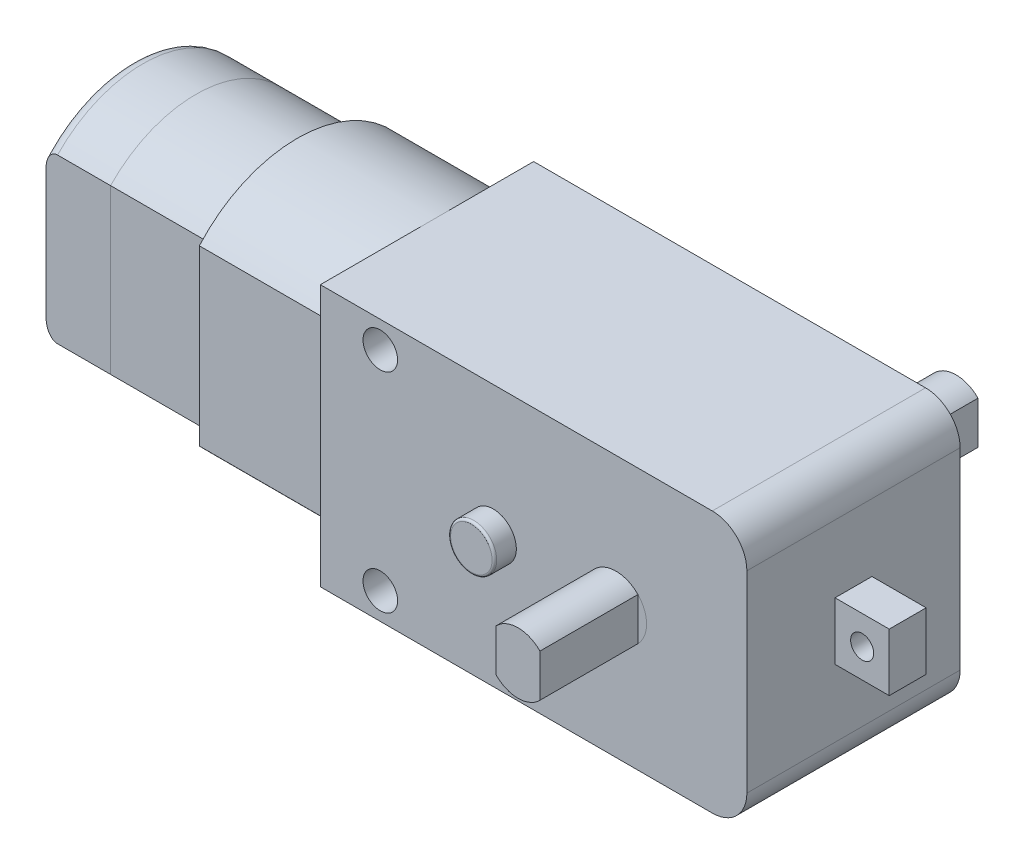
SolidWorks part; units mm, degrees
ref_plane "Alzado" through (0, 0, 0) normal (0, 0, 1) x (1, 0, 0)
ref_plane "Planta" through (0, 0, 0) normal (0, 1, 0) x (1, 0, 0)
ref_plane "Vista lateral" through (0, 0, 0) normal (1, 0, 0) x (0, 0, -1)
sketch "Croquis1" plane through (0, 0, 0) normal (0, 0, 1) x (1, 0, 0)
  line L1 (-18.5, -11.35) -> (15.5, -11.35)
  line L2 (-18.5, -11.35) -> (-18.5, 11.35)
  line L3 (-18.5, 11.35) -> (15.5, 11.35)
  line L4 (18.5, -8.35) -> (18.5, 8.35)
  line L5 (-18.5, -11.35) -> (18.5, 11.35) construction
  line L6 (-18.5, 11.35) -> (18.5, -11.35) construction
  arc A0 (15.5, -11.35) -> (18.5, -8.35) centre (15.5, -8.35) ccw
  arc A1 (15.5, 11.35) -> (18.5, 8.35) centre (15.5, 8.35) cw
  point P0 (0, 0)
  dimension "D3" = 3
  dimension "D1" = 22.7
  dimension "D2" = 37
extrude "Saliente-Extruir1" add sketch "Croquis1" along normal blind 9.25 and the other way blind 9.25
sketch "Croquis2" plane through (-18.5, 0, 0) normal (-1, 0, 0) x (0, 0, 1)
  line L0 (-0.75, -11.35) -> (-0.75, 11.35) construction
  line L1 (7.75, -7.5215) -> (7.75, 7.5215)
  line L2 (-9.25, -7.5215) -> (-9.25, 7.5215)
  line L3 (9.25, 11.35) -> (9.25, -11.35) construction
  line L5 (7.75, -12.1318) -> (7.75, 11.35) construction
  line L6 (-9.25, -12.1318) -> (-9.25, 11.35) construction
  line L7 (-0.75, -12.1318) -> (-0.75, 11.35) construction
  arc A0 (7.75, 7.5215) -> (-9.25, 7.5215) centre (-0.75, 0) ccw
  arc A1 (-9.25, -7.5215) -> (7.75, -7.5215) centre (-0.75, 0) ccw
  point P8 (-0.75, 0)
  dimension "D1" = 22.7
  dimension "D2" = 8.5
  dimension "D3" = 8.5
  dimension "D4" = 1.5
extrude "Saliente-Extruir2" add sketch "Croquis2" along normal blind 12
sketch "Croquis3" plane through (18.5, 0, 0) normal (1, 0, 0) x (0, 0, -1)
  line L1 (1.6, -2.5) -> (-1.6, -2.5)
  line L2 (1.6, -2.5) -> (1.6, 2.5)
  line L3 (1.6, 2.5) -> (-1.6, 2.5)
  line L4 (-1.6, -2.5) -> (-1.6, 2.5)
  line L5 (1.6, -2.5) -> (-1.6, 2.5) construction
  line L6 (1.6, 2.5) -> (-1.6, -2.5) construction
  point P0 (0, 0)
  dimension "D1" = 5
  dimension "D2" = 3.2
extrude "Saliente-Extruir3" add sketch "Croquis3" along normal blind 4.7
sketch "Croquis4" plane through (0, 0, 0) normal (0, 0, 1) x (1, 0, 0)
  line L0 (0, 0) -> (-18.2045, 0) construction
  line L1 (-18.5, -11.35) -> (15.5, -11.35) construction
  line L2 (15.5, 11.35) -> (-18.5, 11.35) construction
  line L3 (-18.5, 11.35) -> (-18.5, -11.35) construction
  circle A0 centre (-13.3, 9.05) radius 1.5
  circle A1 centre (-13.3, -9.05) radius 1.5
  dimension "D1" = 3
  dimension "D2" = 2.3
  dimension "D3" = 2.3
  dimension "D4" = 5.2
  dimension "D5" = 5.2
extrude "Cortar-Extruir1" cut sketch "Croquis4" against normal blind 17.7 and the other way blind 28
sketch "Croquis5" plane through (0, 0, 9.25) normal (0, 0, 1) x (1, 0, 0)
  line L0 (18.5, -8.35) -> (18.5, 8.35) construction
  circle A0 centre (-3.5, 0) radius 2
  point P6 (18.5, 0)
  dimension "D1" = 4
  dimension "D2" = 22
extrude "Saliente-Extruir4" add sketch "Croquis5" along normal blind 1.9
fillet "Redondeo1" radius 0.2 1 edges at (-1.5, 0, 11.15)
sketch "Croquis6" plane through (0, 0, 9.25) normal (0, 0, 1) x (1, 0, 0)
  line L0 (18.5, -8.35) -> (18.5, 8.35) construction
  circle A0 centre (7.15, 0) radius 2.65
  dimension "D1" = 5.3
  dimension "D2" = 11.35
extrude "Cortar-Extruir2" cut sketch "Croquis6" against normal blind 23.9
sketch "Croquis9" plane through (-30.5, 0, 0) normal (-1, 0, 0) x (0, 0, 1)
  line L2 (6.65, -7.5215) -> (6.65, 7.5215)
  line L3 (6.65, -7.0924) -> (6.65, 7.0924)
  line L5 (-8.15, 7.5215) -> (-8.15, -7.5215)
  line L6 (-8.15, 7.0924) -> (-8.15, -7.0924)
  arc A2 (6.9262, 6.7925) -> (-8.4262, 6.7925) centre (-0.75, 0) ccw
  arc A3 (6.65, 7.0924) -> (-8.15, 7.0924) centre (-0.75, 0) ccw
  arc A5 (-8.4262, -6.7925) -> (6.9262, -6.7925) centre (-0.75, 0) ccw
  arc A6 (-8.15, -7.0924) -> (6.65, -7.0924) centre (-0.75, 0) ccw
  dimension "D1" = 1.1
  dimension "D2" = 1.1
  dimension "D3" = 1.1
  dimension "D4" = 1.1
extrude "Saliente-Extruir5" add sketch "Croquis9" along normal blind 8.8 separate body
sketch "Croquis10" plane through (-39.3, 0, 0) normal (-1, 0, 0) x (0, 0, 1)
  line L0 (-8.15, 7.0924) -> (-8.15, -7.0924)
  line L1 (6.65, 7.0924) -> (6.65, -7.0924)
  line L2 (6.65, -7.0924) -> (6.65, 7.0924) construction
  arc A0 (6.65, 7.0924) -> (-8.15, 7.0924) centre (-0.75, 0) ccw
  arc A1 (6.65, 7.0924) -> (-8.15, 7.0924) centre (-0.75, 0) ccw construction
  arc A2 (-8.15, -7.0924) -> (6.65, -7.0924) centre (-0.75, 0) ccw
extrude "Saliente-Extruir6" add sketch "Croquis10" along normal blind 5.6 separate body
fillet "Redondeo2" radius 1 2 edges at (-44.9, 10.25, -0.75) (-44.9, -10.25, -0.75)
sketch "Croquis11" plane through (-44.9, 0, 0) normal (-1, 0, 0) x (0, 0, 1)
  line L0 (6.65, 5.55) -> (6.65, -7.0924) construction
  line L1 (6.65, -7.0924) -> (6.65, -5.55) construction
  line L2 (2.65, 3.6661) -> (2.65, -3.6661)
  line L3 (2.65, 5.55) -> (2.65, -7.0924) construction
  arc A0 (2.65, 3.6661) -> (2.65, -3.6661) centre (-0.75, 0) ccw
  arc A2 (6.65, 7.0924) -> (-8.15, 7.0924) centre (-0.75, 0) ccw construction
  dimension "D1" = 10
  dimension "D2" = 4
extrude "Saliente-Extruir7" add sketch "Croquis11" along normal blind 2 separate body
sketch "Croquis12" plane through (-46.9, 0, 0) normal (-1, 0, 0) x (0, 0, 1)
  circle A0 centre (-0.75, 0) radius 1
  arc A1 (2.65, 3.6661) -> (2.65, -3.6661) centre (-0.75, 0) ccw construction
  dimension "D1" = 2
extrude "Saliente-Extruir8" add sketch "Croquis12" along normal blind 1 separate body
sketch "Croquis13" plane through (0, 0, -8.15) normal (0, 0, -1) x (-1, 0, 0)
  line L0 (44.9, 5.55) -> (44.9, -5.55) construction
  line L1 (39.3, -4) -> (42.3, -4)
  line L2 (39.3, -4) -> (39.3, 4)
  line L3 (39.3, 4) -> (42.3, 4)
  line L4 (42.3, -4) -> (42.3, 4)
  line L5 (39.3, -4) -> (42.3, 4) construction
  line L6 (39.3, 4) -> (42.3, -4) construction
  line L7 (39.3, 7.0924) -> (39.3, -7.0924) construction
  point P0 (40.8, 0)
  point P9 (44.9, 0)
  dimension "D1" = 3
  dimension "D2" = 8
extrude "Saliente-Extruir9" add sketch "Croquis13" along normal blind 1.2 separate body
sketch "Croquis14" plane through (0, 0, 1.6) normal (0, 0, 1) x (1, 0, 0)
  line L0 (18.5, 2.5) -> (23.2, -2.5) construction
  line L1 (23.2, 2.5) -> (18.5, -2.5) construction
  circle A0 centre (20.85, 0) radius 1
  dimension "D1" = 2
extrude "Cortar-Extruir3" cut sketch "Croquis14" against normal blind 4.2
sketch "Croquis15" plane through (0, 0, 0) normal (0, 0, 1) x (1, 0, 0)
  line L0 (7.15, -5.2054) -> (7.15, 5.2054) construction
  line L1 (9.05, -1.8473) -> (9.05, 1.8473)
  line L2 (5.25, -1.8473) -> (5.25, 1.8473)
  line L3 (9.05, -5.2054) -> (9.05, 5.2054) construction
  line L4 (5.25, -5.2054) -> (5.25, 5.2054) construction
  arc A0 (5.25, -1.8473) -> (9.05, -1.8473) centre (7.15, 0) ccw
  circle A1 centre (7.15, 0) radius 2.65 construction
  arc A2 (9.05, 1.8473) -> (5.25, 1.8473) centre (7.15, 0) ccw
  point P7 (7.15, 0)
  dimension "D1" = 1.9
  dimension "D2" = 1.9
extrude "Saliente-Extruir10" add sketch "Croquis15" along normal blind 17.75 and the other way blind 20.25 separate body
sketch "Croquis16" plane through (0, 0, 0) normal (0, 0, 1) x (1, 0, 0)
  circle A0 centre (7.15, 0) radius 2.65
  circle A1 centre (7.15, 0) radius 2.65 construction
extrude "Saliente-Extruir11" add sketch "Croquis16" along normal up to surface (9.25 mm away) and the other way blind 12.25 separate body up to face at (9.8, 0, 9.25)
